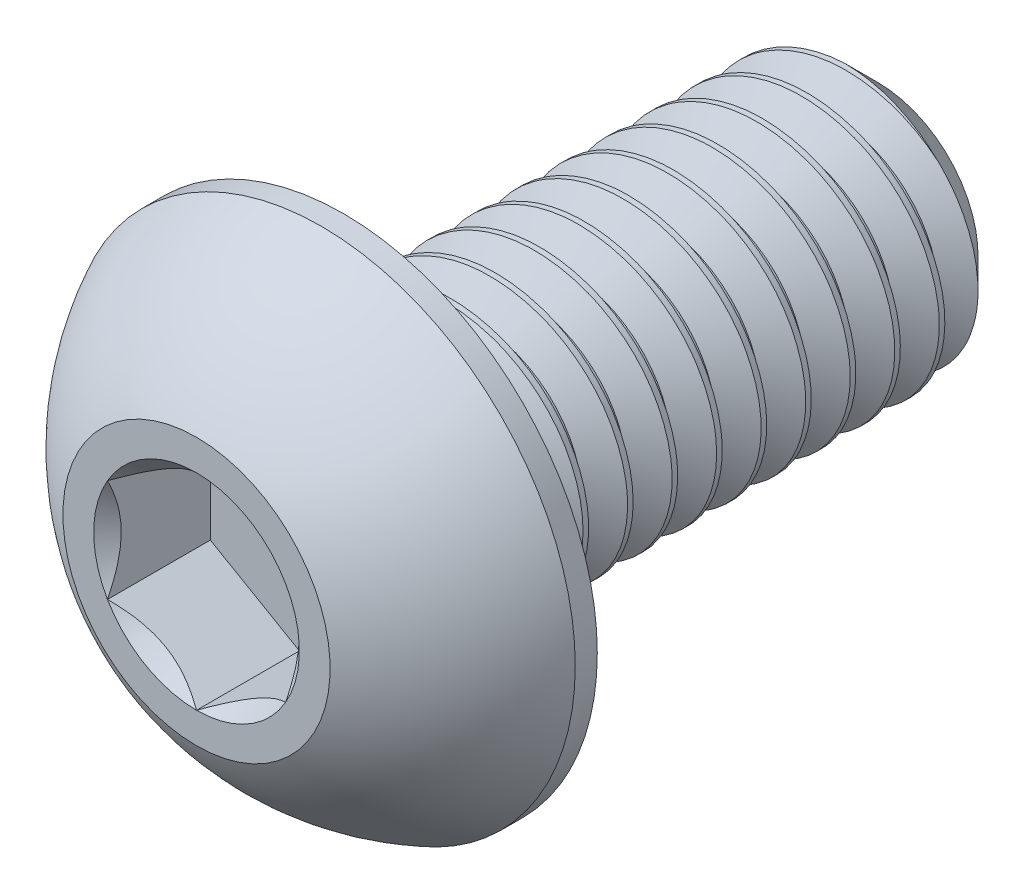
SolidWorks part; units mm, degrees
note: '?' marks a value the reader was unsure of.
ref_plane "Front" through (0, 0, 0) normal (0, 0, 1) x (1, 0, 0)
ref_plane "Top" through (0, 0, 0) normal (0, 1, 0) x (1, 0, 0)
ref_plane "Right" through (0, 0, 0) normal (1, 0, 0) x (0, 0, -1)
sketch "Sketch1" plane through (0, 0, 0) normal (1, 0, 0) x (0, 0, -1)
  line L2 (1.65, 1.5) -> (7.65, 1.5)
  line L3 (7.65, 1.5) -> (7.65, 0)
  line L4 (7.65, 0) -> (1.65, 0)
  line L6 (1.4025, 2.85) -> (1.65, 2.85) construction
  line L7 (7.65, 1.5) -> (7.65, -1.5) construction
  line L8 (0, 0) -> (1.65, 0) construction
  line L9 (1.65, 2.85) -> (1.65, -2.85) construction
  line L11 (1.65, 1.5) -> (1.65, 0)
  line L13 (0, 1) -> (0, -1) construction
  line L14 (0, 1) -> (0, 1.5) construction
  arc A3 (0, 1.5) -> (1.4025, 2.85) centre (2.7948, 0) cw construction
  dimension "D1" = 0.2475
  dimension "Head Ht" = 1.65
  dimension "Head Dia" = 5.7
  dimension "Dia" = 3
  dimension "Lg" = 6
  dimension "Hex" = 2
revolve "Revolve1" add sketch "Sketch1" angle 360 mid plane about L4
sketch "Sketch3" plane through (0, 0, -7.65) normal (0, 0, -1) x (-1, 0, 0)
  circle A0 centre (0, 0) radius 1.5
curve "Helix/Spiral1" pitch 0.5 height 6.5 turns 13
chamfer "Chamfer1" distance 0.375 angle 45 1 edges at (0, 1.5, -7.65)
sketch "Sketch7" plane through (0, 0, 0) normal (1, 0, 0) x (0, 0, -1)
  line L6 (1.4025, 2.85) -> (1.65, 2.85) construction
  line L8 (0, 0) -> (1.65, 0) construction
  line L11 (1.65, 2.85) -> (1.65, -2.85) construction
  line L12 (1.4025, 2.85) -> (1.65, 2.85)
  line L13 (0, 0) -> (1.65, 0)
  line L14 (0, 1) -> (0, -1) construction
  line L15 (1.65, 2.85) -> (1.65, 0)
  line L16 (0, 1.5) -> (0, 0)
  arc A2 (1.4025, 2.85) -> (0, 1.5) centre (2.7948, 0) ccw construction
  arc A3 (1.4025, 2.85) -> (0, 1.5) centre (2.7948, 0) ccw
revolve "Revolve2" add sketch "Sketch7" angle 360 mid plane about L13
sketch "Sketch5" plane through (0, 0, 0) normal (0, 0, 1) x (1, 0, 0)
  line L1 (1, -0.5774) -> (1, 0.5774)
  line L2 (1, 0.5774) -> (0, 1.1547)
  line L3 (0, 1.1547) -> (-1, 0.5774)
  line L4 (-1, 0.5774) -> (-1, -0.5774)
  line L5 (-1, -0.5774) -> (0, -1.1547)
  line L6 (0, -1.1547) -> (1, -0.5774)
  circle A0 centre (0, 0) radius 1 construction
extrude "Cut-Extrude2" cut sketch "Sketch5" against normal blind 1.155
sketch "Sketch6" plane through (0, 0, 0) normal (0, 0, 1) x (1, 0, 0)
  circle A0 centre (0, 0) radius 1.1547
extrude "Cut-Extrude3" cut sketch "Sketch6" against normal blind 1.155 draft 45
sketch "Sketch2" plane through (0, 0, 0) normal (1, 0, 0) x (0, 0, -1)
  line L0 (7.275, 1.5) -> (7.7125, 1.5)
  line L1 (7.7125, 1.5) -> (7.525, 1.1752)
  line L2 (7.525, 1.1752) -> (7.4625, 1.1752)
  line L3 (7.4625, 1.1752) -> (7.275, 1.5)
  line L4 (7.3687, 1.3376) -> (7.6187, 1.3376) construction
  dimension "D1" = 60
  dimension "D2" = 0.0625
  dimension "D3" = 0.25
sweep "Cut-Sweep1" cut profiles "Sketch2" path "Helix/Spiral1"
sketch "Sketch10" plane through (0, 0, 0) normal (1, 0, 0) x (0, 0, -1)
  line L0 (7.65, 1.5) -> (7.65, -1.5) construction
  point P0 (6.9, -1.5)
  dimension "D1" = 0.75
ref_axis "Center Axis 1" through (0, 0, -8.1113) along (0, 0, 1)?
ref_plane "Contact Plane 1" through (0, 0, -1.65) normal (0, 0, -1) x (-1, 0, 0)
ref_plane "Contact Plane 2" through (0, 0, 0) normal (0, 0, 1) x (1, 0, 0)
equation "\"D3@Helix/Spiral1\" = \"Lg@Sketch1\" + \"D4@Helix/Spiral1\""
equation "\"D2@Sketch2\" = \"D4@Helix/Spiral1\" * .125"
equation "\"D3@Sketch2\" = \"D4@Helix/Spiral1\" * .5"
equation "\"D1@Chamfer1\" = \"D4@Helix/Spiral1\" * .75"
equation "\"D1@Cut-Extrude2\" = \"Head Ht@Sketch1\" * .7"
equation "\"D1@Sketch1\" = \"Head Ht@Sketch1\" * .15"
equation "\"D1@Sketch10\" = \"D4@Helix/Spiral1\" * 1.5"
equation "\"D1@Cut-Extrude3\" = \"D1@Cut-Extrude2\""
